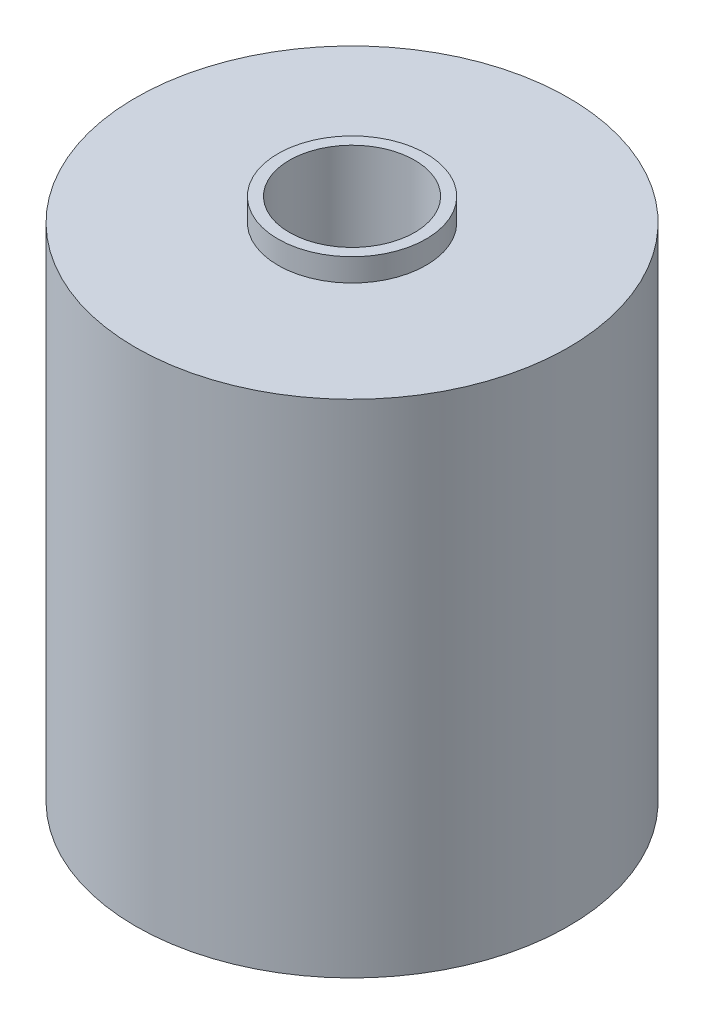
SolidWorks part; units mm, degrees
ref_plane "Plano frontal" through (0, 0, 0) normal (0, 0, 1) x (1, 0, 0)
ref_plane "Plano superior" through (0, 0, 0) normal (0, 1, 0) x (1, 0, 0)
ref_plane "Plano direito" through (0, 0, 0) normal (1, 0, 0) x (0, 0, -1)
sketch "Esboço1" plane through (0, 0, 0) normal (0, 1, 0) x (1, 0, 0)
  circle A0 centre (0, 0) radius 3.25
  circle A1 centre (0, 0) radius 9.5
  circle A2 centre (0, 0) radius 2.75
  dimension "D1" = 6.5
  dimension "D2" = 19
  dimension "D3" = 5.5
extrude "Ressalto-extrusão1" add sketch "Esboço1" along normal mid plane 22 contours A1 A0 region at (-9.2313, 0, 0)
extrude "Ressalto-extrusão2" add sketch "Esboço1<3>" along normal mid plane 24 contours A0 A2 region at (-3.1581, 0, 0)
sketch "Esboço1<3>" plane through (0, 0, 0) normal (0, 1, 0) x (1, 0, 0) same geometry as "Esboço1"
